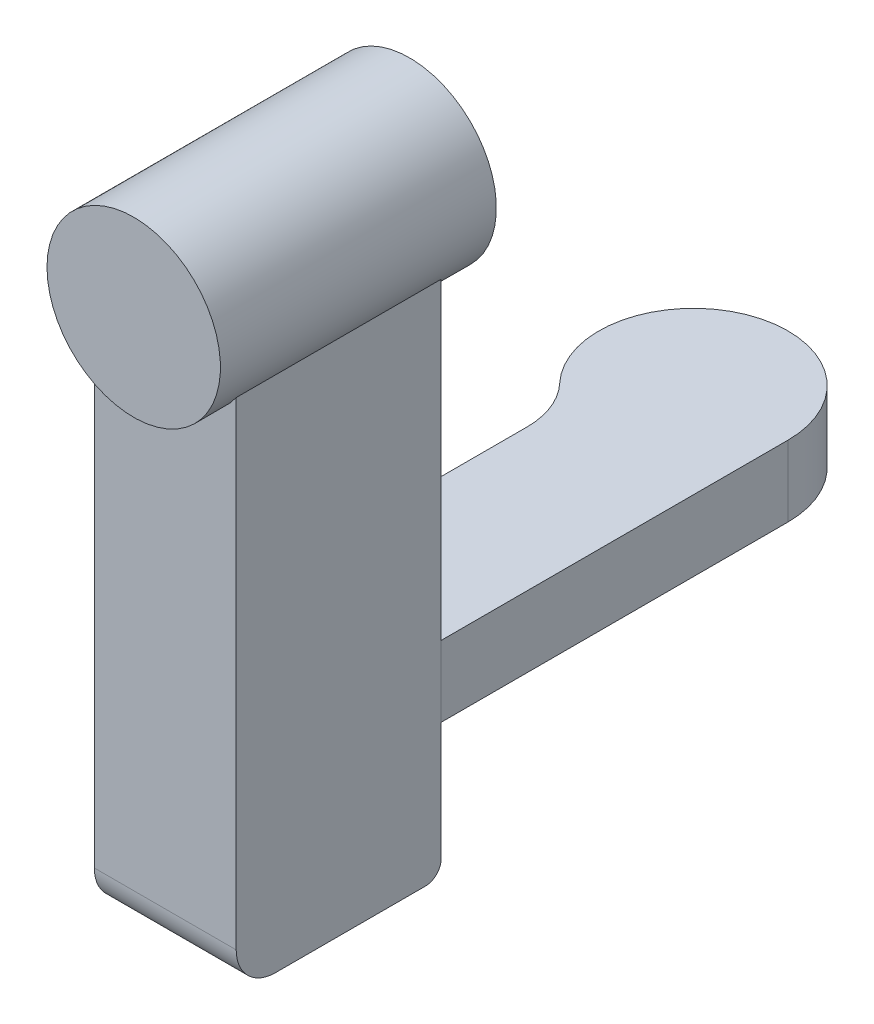
SolidWorks part; units mm, degrees
ref_plane "Front Plane" through (0, 0, 0) normal (0, 0, 1) x (1, 0, 0)
ref_plane "Top Plane" through (0, 0, 0) normal (0, 1, 0) x (1, 0, 0)
ref_plane "Right Plane" through (0, 0, 0) normal (1, 0, 0) x (0, 0, -1)
sketch "Sketch1" plane through (0, 0, 0) normal (0, 1, 0) x (1, 0, 0)
  line L0 (12, 0) -> (12, -44)
  line L1 (12, -44) -> (-6, -44)
  line L2 (-6, -44) -> (-6, -15.0997)
  arc A0 (12, 0) -> (-8.7273, -8.2362) centre (0, 0) ccw
  arc A1 (-6, -15.0997) -> (-8.7273, -8.2362) centre (-16, -15.0997) ccw
  dimension "D1" = 10
extrude "Boss-Extrude1" add sketch "Sketch1" along normal blind 9
ref_plane "Plane2" through (0, 9, 0) normal (0, 1, 0) x (1, 0, 0)
sketch "Sketch2" plane through (0, 9, 0) normal (0, 1, 0) x (1, 0, 0)
  line L1 (12, -44) -> (-6, -44)
  line L2 (12, -44) -> (12, -70)
  line L3 (12, -70) -> (-6, -70)
  line L4 (-6, -44) -> (-6, -70)
  dimension "D1" = 26
extrude "Boss-Extrude2" add sketch "Sketch2" along normal blind 40 and the other way blind 26 separate body
fillet "Fillet2" radius 2 1 edges at (3, -17, 44) type face fillet first side face at (3, 16, 44) second side face at (3, -17, 57)
fillet "Fillet3" radius 5 1 edges at (3, -17, 70) type face fillet first side face at (3, -17, 58) second side face at (3, 16, 70)
ref_plane "Plane3" through (0, 0, 44) normal (0, 0, -1) x (-1, 0, 0)
sketch "Sketch3" plane through (0, 0, 44) normal (0, 0, -1) x (-1, 0, 0)
  line L0 (-12, 49) -> (6, 49) construction
  circle A0 centre (-3, 55) radius 11
  dimension "D1" = 6
extrude "Boss-Extrude3" add sketch "Sketch3" along normal blind 5 and the other way blind 30
ref_point "Point1"
ref_point "Point2"
ref_axis "Axis1" through (0, 0, 0) along (0, 1, 0)
ref_point "Point3"
